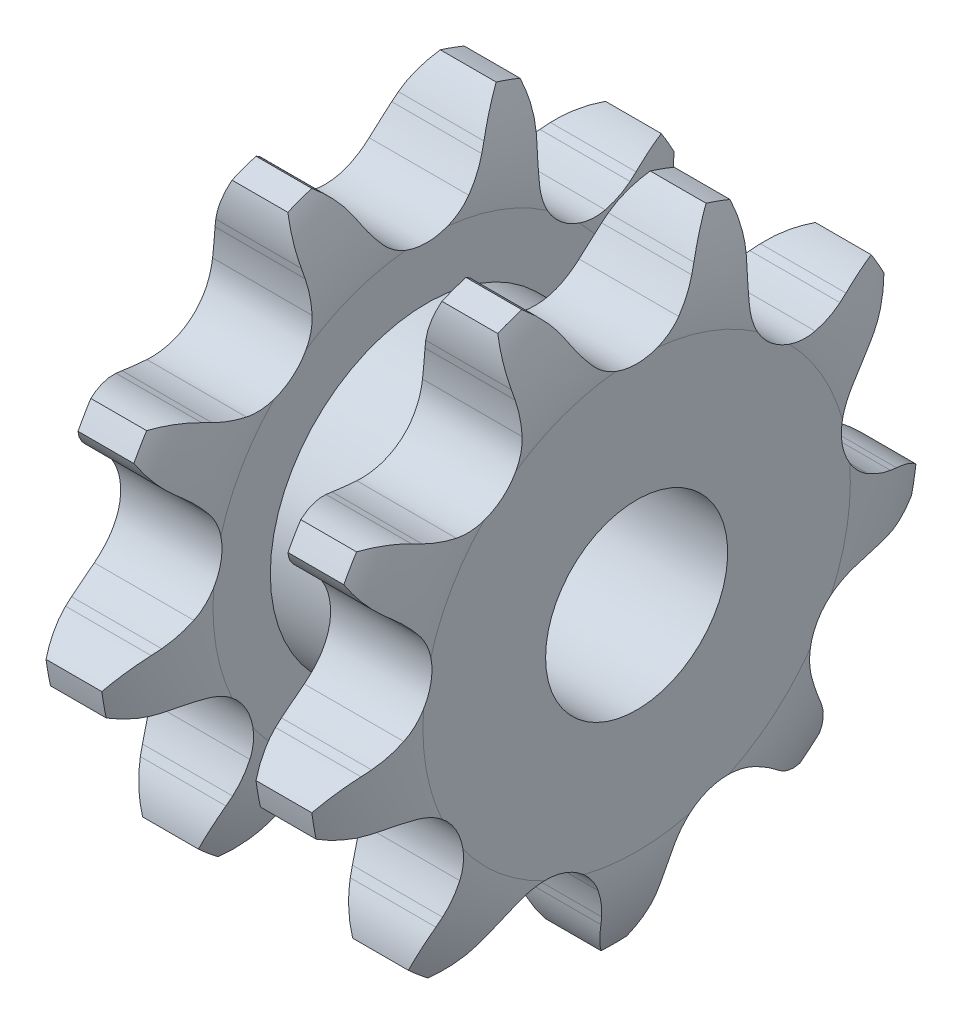
SolidWorks part; units mm, degrees
ref_plane "Plane1" through (0, 0, 0) normal (0, 0, 1) x (1, 0, 0)
ref_plane "Plane2" through (0, 0, 0) normal (0, 1, 0) x (1, 0, 0)
ref_plane "Plane3" through (0, 0, 0) normal (1, 0, 0) x (0, 0, -1)
sketch "Clipboard" plane through (0, 0, 0) normal (0, 1, 0) x (1, 0, 0)
  line L0 (0, 0) -> (25.0873, -3.9734)
  line L1 (-15, 0) -> (100, 0) construction
  line L2 (0, 0) -> (-2.1039, 2.3779)
  line L3 (0, 0) -> (-11.863, 4.5341)
  line L4 (0, 0) -> (15.6796, 2.4834)
  line L5 (0, 0) -> (-47.5972, -17.7524)
  line L6 (0, 0) -> (-35.9946, -24.2857)
  line L7 (-2.1039, 2.3779) -> (47.7628, 12.071)
  line L8 (-76.2, 38.1) -> (-47.9044, 38.1)
  line L9 (-73.2054, 38.5461) -> (-73.0531, 38.5485)
  line L10 (-73.0533, 76.1892) -> (-43.7671, 76.1892)
  circle A0 centre (0, 0) radius 7.9375
  circle A1 centre (0, 0) radius 21.812
  circle A2 centre (0, 0) radius 25.4
  dimension "Num_teeth" = 9
  dimension "Thickness" = 43.4213
sketch "BasProSke" plane through (0, 0, 0) normal (0, 1, 0) x (1, 0, 0)
  line L0 (-10, 0) -> (60, 0) construction
  line L1 (0, 0) -> (0, 29.813)
  line L2 (0, 0) -> (43.4213, 0)
  line L3 (43.4213, 0) -> (43.4213, 29.813)
  line L4 (40.2463, 42.513) -> (3.175, 42.513)
  arc A0 (0, 29.813) -> (3.175, 42.513) centre (26.9875, 29.813) cw
  arc A1 (43.4213, 29.813) -> (40.2463, 42.513) centre (16.4338, 29.813) ccw
  dimension "D1" = 26.9875
  dimension "Thickness" = 43.4213
  dimension "Diameter" = 85.0259
  dimension "H1" = 12.7
  dimension "G1" = 3.175
revolve "Base-Revolve" add sketch "BasProSke" angle 360 about L0
sketch "GrvSke" plane through (0, 0, 0) normal (0, 1, 0) x (1, 0, 0)
  line L0 (14.1351, 29.813) -> (14.1351, 21.812)
  line L1 (14.1351, 21.812) -> (29.2862, 21.812)
  line L2 (29.2862, 21.812) -> (29.2862, 29.813)
  line L3 (10.9601, 42.513) -> (32.4612, 42.513)
  line L4 (21.7106, 0) -> (21.7106, 52.07) construction
  line L5 (-10, 0) -> (60, 0) construction
  line L6 (0, 0) -> (35.56, 0) construction
  arc A0 (29.2862, 29.813) -> (32.4612, 42.513) centre (56.2737, 29.813) cw
  arc A1 (14.1351, 29.813) -> (10.9601, 42.513) centre (-12.8524, 29.813) ccw
  dimension "Diameter" = 85.0259
  dimension "H1" = 12.7
  dimension "G1" = 3.175
revolve "Groove" cut sketch "GrvSke" angle 360 about L6
pattern_linear "Grooves" [suppressed]
sketch "TooCutSke" plane through (0, 0, 0) normal (1, 0, 0) x (0, 0, -1)
  line L0 (8.4728, 35.2524) -> (9.083, 36.3141)
  line L1 (0, 0) -> (0, 107) construction
  line L2 (0, 37.1323) -> (-10, 37.1323) construction
  line L3 (-8.4728, 35.2524) -> (-9.083, 36.3141)
  arc A0 (5.9876, 31.8038) -> (8.4728, 35.2524) centre (-9.4872, 45.5752) ccw
  arc A1 (5.9876, 31.8038) -> (-5.9876, 31.8038) centre (0, 37.1323) cw
  arc A2 (9.083, 36.3141) -> (20.8847, 43.143) centre (20.8847, 29.5309) cw
  arc A3 (-5.9876, 31.8038) -> (-8.4728, 35.2524) centre (9.4872, 45.5752) cw
  arc A4 (-9.083, 36.3141) -> (-20.8847, 43.143) centre (-20.8847, 29.5309) ccw
  arc A5 (20.8847, 43.143) -> (-20.8847, 43.143) centre (0, 0) ccw
  dimension "Pitch_radius" = 37.1323
  dimension "V" = 7.6014
extrude "ToothCut" cut sketch "TooCutSke" along normal through all
pattern_circular "TeethCuts" count 9 every 40 about axis through (-10, 0, 0) along (1, 0, 0) of "ToothCut"
sketch "HubNeaOneSke" plane through (0, 0, 0) normal (-1, 0, 0) x (0, 0, 1)
  circle A0 centre (0, 0) radius 21.812
  dimension "Diameter" = 43.6239
extrude "HubNearOne" [suppressed] add sketch "HubNeaOneSke" along normal blind 7.3788
sketch "HubNeaBotSke" plane through (0, 0, 0) normal (-1, 0, 0) x (0, 0, 1)
  circle A0 centre (0, 0) radius 21.812
  dimension "Diameter" = 43.6239
extrude "HubNearBoth" [suppressed] add sketch "HubNeaBotSke" along normal blind 3.6894
ref_plane "FarPln" through (43.4213, 0, 0) normal (1, 0, 0) x (0, 0, -1)
sketch "HubFarSke" plane through (43.4213, 0, 0) normal (1, 0, 0) x (0, 0, -1)
  circle A0 centre (0, 0) radius 21.812
  dimension "Diameter" = 43.6239
extrude "HubFar" [suppressed] add sketch "HubFarSke" along normal blind 3.6894
sketch "BorSke" plane through (0, 0, 0) normal (1, 0, 0) x (0, 0, -1)
  circle A0 centre (0, 0) radius 12.7
  dimension "Diameter" = 25.4
extrude "Bore" cut sketch "BorSke" along normal mid plane 101.6001
sketch "KeySke" plane through (0, 0, 0) normal (1, 0, 0) x (0, 0, -1)
  line L0 (-3.175, 0) -> (-3.175, 15.5956)
  line L1 (-3.175, 15.5956) -> (3.175, 15.5956)
  line L2 (3.175, 15.5956) -> (3.175, 0)
  line L3 (0, 0) -> (0, 34) construction
  line L4 (-3.175, 0) -> (3.175, 0)
  dimension "Offset" = 15.5956
  dimension "Width" = 6.35
extrude "Keyway" [suppressed] cut sketch "KeySke" along normal mid plane 101.6001
pattern_circular "Keyway2" [suppressed] count 2 every 90 about axis through (-10, 0, 0) along (1, 0, 0) reverse direction yes
equation "\"Num_teeth@Clipboard\" = int( \"Num_teeth@Clipboard\" )"
equation "\"Num_teeth@Clipboard\" = ((sgn( \"Num_teeth@Clipboard\" - 5.0)+1)*( \"Num_teeth@Clipboard\" - 5.0))/2 +5.0"
equation "\"Num_teeth@Clipboard\" = ((sgn( \"Num_teeth@Clipboard\" - 200.0)-1)*( \"Num_teeth@Clipboard\" - 200.0))/-2 +200.0"
equation "\"MHD@Clipboard\" = \"Pitch@Clipboard\" * (1.0 / tan(3.14159265 / \"Num_teeth@Clipboard\" ) - 1.0) - 0.03"
equation "\"Thickness@Clipboard\"  = \"Width@Clipboard\" * \"Width_factor@Clipboard\" - \"Width_const@Clipboard\" + (\"Num_strands@Clipboard\" - 1) * \"Transv_pitch@Clipboard\""
equation "\"OAL@Clipboard\" = \"Thickness@Clipboard\""
equation "\"MHD@Clipboard\" = ((sgn( \"MHD@Clipboard\" - \"Hub_dia@Clipboard\" )-1)*( \"MHD@Clipboard\" - \"Hub_dia@Clipboard\" ))/-2+ \"Hub_dia@Clipboard\""
equation "\"OAL@Clipboard\" = ((sgn( \"OAL@Clipboard\" - \"Overall_len@Clipboard\" )+1)*( \"OAL@Clipboard\" - \"Overall_len@Clipboard\" ))/2 + \"Overall_len@Clipboard\" + 0.000002"
equation "\"Num_teeth@TeethCuts\" = int( \"Show_teeth@Clipboard\" ) + 1"
equation "\"Num_teeth@TeethCuts\" = ((sgn( \"Num_teeth@TeethCuts\" - \"Num_teeth@Clipboard\" )-1)*( \"Num_teeth@TeethCuts\" - \"Num_teeth@Clipboard\" ))/-2+ \"Num_teeth@Clipboard\""
equation "\"Num_teeth@TeethCuts\" = ((sgn( \"Num_teeth@TeethCuts\" - 2.0)+1)*( \"Num_teeth@TeethCuts\" - 2.0))/2 +2.0"
equation "\"Angle@TeethCuts\" = 360.0 / \"Num_teeth@Clipboard\""
equation "\"Pitch_radius@TooCutSke\" = ( \"Pitch@Clipboard\" / 2.0) / sin(3.14159265 / \"Num_teeth@Clipboard\" )  'ma"
equation "\"R@TooCutSke\"  = \"Dr@Clipboard\" * 0.5025 + 0.0015"
equation "\"A@TooCutSke\" = 35.0 + (60.0 / \"Num_teeth@Clipboard\")"
equation "\"E@TooCutSke\"  = \"Dr@Clipboard\" * 1.3025 + 0.0015"
equation "\"B@TooCutSke\"  = 18.0 - (56.0 / \"Num_teeth@Clipboard\" )"
equation "\"W@TooCutSke\" = 1.4 * \"Dr@Clipboard\" * cos(3.14159265 / \"Num_teeth@Clipboard\" )"
equation "\"V@TooCutSke\" = 1.4 * \"Dr@Clipboard\" * sin(3.14159265 / \"Num_teeth@Clipboard\" )"
equation "\"Diameter@BasProSke\" = 2.0 * ( (0.3 * \"Pitch@Clipboard\" ) +  \"Pitch@Clipboard\" / 2.0 / tan(3.14159265 / \"Num_teeth@Clipboard\" ))"
equation "\"Thickness@BasProSke\"  = \"Thickness@Clipboard\""
equation "\"G1@BasProSke\" =  \"Chamfer_wid@Clipboard\""
equation "\"G2@BasProSke\" =  \"Chamfer_wid@Clipboard\""
equation "\"H1@BasProSke\" =  \"Chamfer_dep@Clipboard\""
equation "\"H2@BasProSke\" =  \"Chamfer_dep@Clipboard\""
equation "\"Diameter@GrvSke\" = \"Diameter@BasProSke\""
equation "\"G1@GrvSke\" = \"Chamfer_wid@Clipboard\""
equation "\"H1@GrvSke\" = \"Chamfer_dep@Clipboard\""
equation "\"Grv_diam@GrvSke\" =  \"Pitch@Clipboard\" * (1.0 / tan(3.14159265 / \"Num_teeth@Clipboard\" ) - 1.0) - 0.03"
equation "\"Grv_width@GrvSke\" =  \"Transv_pitch@Clipboard\" - ( \"Width@Clipboard\" * \"Width_factor@Clipboard\" - \"Width_const@Clipboard\" )"
equation "\"Offset@GrvSke\" = \"Grv_width@GrvSke\" / 2.0 + ( \"Width@Clipboard\" * \"Width_factor@Clipboard\" - \"Width_const@Clipboard\" )"
equation "\"Offset@Grooves\" = \"Transv_pitch@Clipboard\""
equation "\"Num_grvs@Grooves\" = \"Num_strands@Clipboard\""
equation "\"Num_grvs@Grooves\" = \"Num_grvs@Grooves\" - 1 * sgn( \"Num_grvs@Grooves\" -1)"
equation "\"Diameter@HubNeaOneSke\" = \"MHD@Clipboard\""
equation "\"Length@HubNearOne\" = \"OAL@Clipboard\" - \"Thickness@BasProSke\""
equation "\"Diameter@HubNeaBotSke\" = \"MHD@Clipboard\""
equation "\"Length@HubNearBoth\" = ( \"OAL@Clipboard\" - \"Thickness@BasProSke\" ) / 2.0"
equation "\"Thickness@FarPln\" = \"Thickness@BasProSke\""
equation "\"Diameter@HubFarSke\" = \"MHD@Clipboard\""
equation "\"Length@HubFar\" = ( \"OAL@Clipboard\" - \"Thickness@BasProSke\" ) / 2.0"
equation "\"D1@Bore\" = \"OAL@Clipboard\" * 2.0"
equation "\"D1@Keyway\" = \"OAL@Clipboard\" * 2.0"
equation "\"Offset@KeySke\" = \"T_dim@Clipboard\" - \"Diameter@BorSke\" / 2.0"
